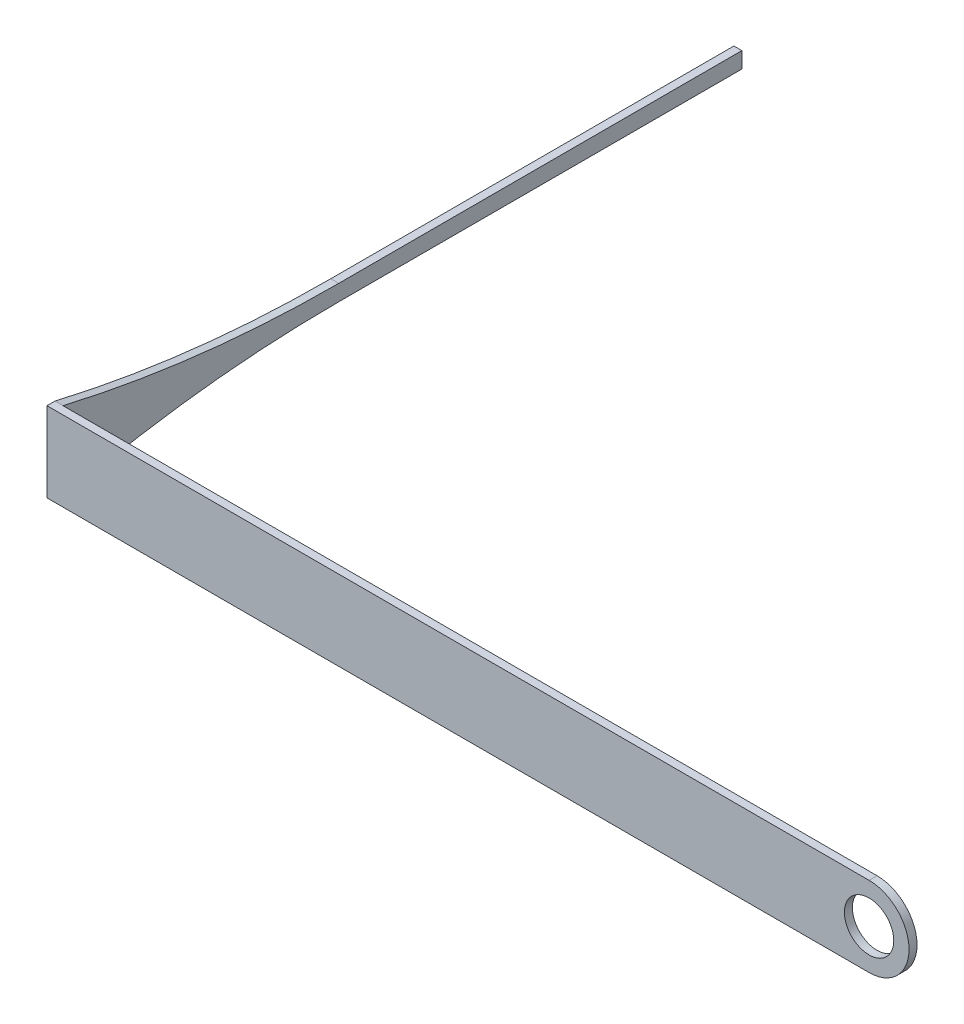
SolidWorks part; units mm, degrees
ref_plane "Front Plane" through (0, 0, 0) normal (0, 0, 1) x (1, 0, 0)
ref_plane "Top Plane" through (0, 0, 0) normal (0, 1, 0) x (1, 0, 0)
ref_plane "Right Plane" through (0, 0, 0) normal (1, 0, 0) x (0, 0, -1)
sketch "Sketch1" plane through (0, 0, 0) normal (0, 1, 0) x (1, 0, 0)
  line L0 (0, 0) -> (-101.9064, 0)
  line L1 (-101.9064, 0) -> (-101.9064, 84.9819)
  line L2 (0, -1) -> (-102.9064, -1)
  line L3 (-102.9064, -1) -> (-102.9064, 84.9819)
  line L4 (0, 0) -> (0, -1)
  line L5 (-102.9064, 84.9819) -> (-101.9064, 84.9819)
  dimension "D1" = 1
extrude "Boss-Extrude1" add sketch "Sketch1" along normal mid plane 10
sketch "Sketch2" plane through (0, 0, 1) normal (0, 0, 1) x (1, 0, 0)
  line L0 (-102.9064, 5) -> (0, 5) construction
  circle A0 centre (0, 0) radius 3.0889
  circle A1 centre (0, 0) radius 5
extrude "Boss-Extrude2" add sketch "Sketch2" against normal up to surface (1 mm away) contours A1 A0 region at (-4.8586, 0, 1) up to face at (-50.9532, 0, 0)
sketch "Sketch3" plane through (0, 0, 1) normal (0, 0, 1) x (1, 0, 0)
  circle A0 centre (0, 0) radius 3.0889
  arc A1 (0, -3.0889) -> (0, 3.0889) centre (0, 0) ccw construction
extrude "Cut-Extrude1" cut sketch "Sketch3" against normal up to surface (1 mm away) up to face at (-49.7032, 0, 0)
ref_axis "Axis1" through (0, 0, 0) along (0, 0, 1)
sketch "Sketch4" plane through (-102.9064, 0, 0) normal (-1, 0, 0) x (0, 0, 1)
  line L0 (-84.9819, -1) -> (-84.9819, 1)
  line L1 (-84.9819, 5) -> (-84.9819, -5) construction
  line L2 (-84.9819, 1) -> (-34.5274, 1)
  line L3 (-84.9819, -1) -> (-34.5274, -1)
  line L4 (-84.9819, 0) -> (-74.9325, 0) construction
  arc A0 (-34.5274, 1) -> (0, 5) centre (-34.5274, 152.0179) ccw
  arc A1 (-34.5274, -1) -> (0, -5) centre (-34.5274, -152.0179) cw
  point P5 (-84.9819, 0)
  line M7 (-84.9819, -5) -> (1, -5)
  line M9 (1, 5) -> (-84.9819, 5)
  line M10 (-84.9819, 5) -> (-84.9819, -5)
  dimension "D1" = 2
extrude "Cut-Extrude2" cut sketch "Sketch4" against normal blind 10 and the other way through all contours L2 A0 M9 M10 | A1 L3 M10 M7 region at (-102.9064, 3.125, -47.7656) region at (-102.9064, -3.125, -47.7656)
